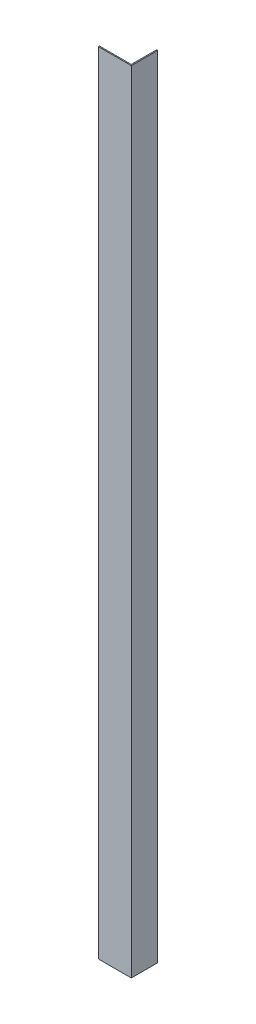
SolidWorks part; units mm, degrees
material "6061-T6 (SS)"
ref_plane "Alzado" through (0, 0, 0) normal (0, 0, 1) x (1, 0, 0)
ref_plane "Planta" through (0, 0, 0) normal (0, 1, 0) x (1, 0, 0)
ref_plane "Vista lateral" through (0, 0, 0) normal (1, 0, 0) x (0, 0, -1)
sketch "Sketch1" plane through (0, 0, 0) normal (0, 1, 0) x (1, 0, 0)
  line L0 (0, 0) -> (15, 0)
  line L1 (15, 0) -> (15, 12)
  line L2 (15, 12) -> (14.5, 12)
  line L3 (14.5, 12) -> (14.5, 0.5)
  line L4 (14.5, 0.5) -> (0, 0.5)
  line L5 (0, 0.5) -> (0, 0)
  dimension "D1" = 15
  dimension "D2" = 12
  dimension "D3" = 0.5
  dimension "D4" = 0.5
extrude "Boss-Extrude1" add sketch "Sketch1" along normal blind 360
